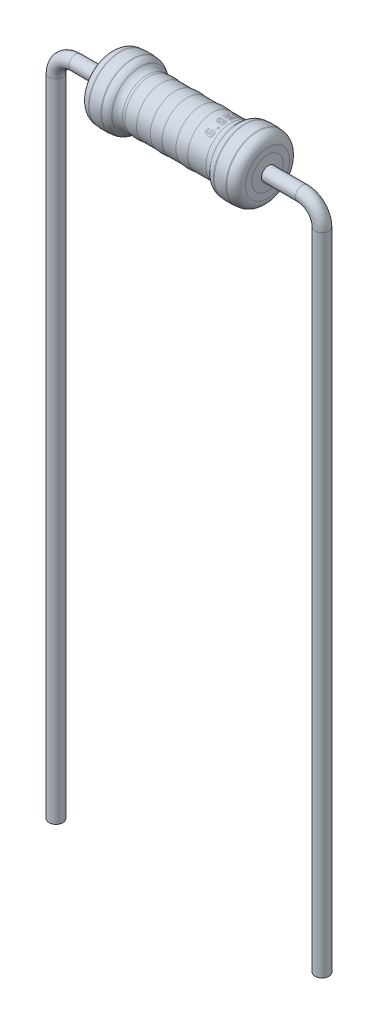
SolidWorks part; units mm, degrees
material "Plain Carbon Steel"
ref_plane "Front Plane" through (0, 0, 0) normal (0, 0, 1) x (1, 0, 0)
ref_plane "Top Plane" through (0, 0, 0) normal (0, 1, 0) x (1, 0, 0)
ref_plane "Right Plane" through (0, 0, 0) normal (1, 0, 0) x (0, 0, -1)
sketch "Sketch1" plane through (0, 0, 0) normal (0, 0, 1) x (1, 0, 0)
  line L0 (-4.33, 0) -> (4.33, 0)
  line L1 (-5.08, -0.75) -> (-5.08, -25.4)
  line L2 (5.08, -0.75) -> (5.08, -25.4)
  line L3 (-5.08, -25.4) -> (5.08, -25.4) construction
  line L4 (0, 0) -> (0, -25.4) construction
  arc A0 (-4.33, 0) -> (-5.08, -0.75) centre (-4.33, -0.75) ccw
  arc A1 (4.33, 0) -> (5.08, -0.75) centre (4.33, -0.75) cw
  dimension "D2" = 0.75
  dimension "D1" = 10.16
  dimension "D3" = 25.4
ref_plane "Plane1" through (-5.08, -25.4, 0) normal (0, -1, 0) x (-1, 0, 0)
sketch "Sketch2" plane through (-5.08, -25.4, 0) normal (0, -1, 0) x (-1, 0, 0)
  circle A0 centre (0, 0) radius 0.265
  dimension "D1" = 0.53
sweep "Sweep1" add profiles "Sketch2" path "Sketch1"
sketch "Sketch3" plane through (0, 0, 0) normal (0, 0, 1) x (1, 0, 0)
  line L0 (-3, 0) -> (3, 0)
  line L5 (-3, 0) -> (-3, 1.2)
  line L6 (3, 0) -> (3, 1.2)
  line L7 (-3, 1.2) -> (-1.8, 1.2)
  line L8 (3, 1.2) -> (1.8, 1.2)
  line L9 (-1.8, 1.2) -> (-1.8, 0.95)
  line L10 (-1.8, 0.95) -> (1.8, 0.95)
  line L11 (1.8, 0.95) -> (1.8, 1.2)
  line L12 (0, 0) -> (0, 0.95) construction
  dimension "D1" = 6
  dimension "D2" = 1.2
  dimension "D3" = 3.6
  dimension "D4" = 0.95
  dimension "D5" = 0.25
revolve "Revolve1" add sketch "Sketch3" angle 360 about L0
fillet "Fillet-1" radius 0.35 2 edges at (1.8, 0, 1.2) (-1.8, 0, 1.2)
fillet "Fillet-2" radius 0.36 4 edges at (3, 0, 1.2) (-3, 0, 1.2) (1.8, 0, 0.95) (-1.8, 0, 0.95)
sketch "Sketch5" plane through (0, 0, 0) normal (0, 0, 1) x (1, 0, 0)
  line L0 (-2.64, -1.2) -> (-2.1354, -1.2) construction
  line L5 (-2.3877, -1.2) -> (-2.3877, 0) construction
  line L10 (-3, 1.2) -> (-1.8, 1.2) construction
  line L15 (-1.05, 0.95) -> (-0.525, 0.95) construction
  line L16 (-3, 0) -> (3, 0) construction
  line L17 (-2.6127, 1.2) -> (-2.1627, 1.2) construction
  line L18 (-2.6127, 1.2) -> (-2.6127, 0) construction
  line L19 (-2.6127, 0) -> (-2.1627, 0) construction
  line L20 (-2.1627, 1.2) -> (-2.1627, 0) construction
  line L21 (-1.8, 0.95) -> (1.8, 0.95) construction
  line L22 (2.6127, 1.2) -> (2.1627, 1.2) construction
  line L23 (2.6127, 1.2) -> (2.6127, 0) construction
  line L24 (2.6127, 0) -> (2.1627, 0) construction
  line L25 (2.1627, 1.2) -> (2.1627, 0) construction
  line L26 (-1.05, 0.95) -> (-1.5, 0.95) construction
  line L27 (-1.05, 0.95) -> (-1.05, 0) construction
  line L28 (-1.05, 0) -> (-1.5, 0) construction
  line L29 (-1.5, 0.95) -> (-1.5, 0) construction
  line L30 (-2.3877, 1.2) -> (-2.3877, 1.22) construction
  line L31 (-0.075, 0.95) -> (-0.525, 0.95) construction
  line L32 (-0.075, 0.95) -> (-0.075, 0) construction
  line L33 (-0.075, 0) -> (-0.525, 0) construction
  line L34 (-0.525, 0.95) -> (-0.525, 0) construction
  line L35 (-1.275, 0.95) -> (-1.275, 0.97) construction
  line L36 (-0.3, 0.95) -> (-0.3, 0.97) construction
  line L37 (2.3877, 1.2) -> (2.3877, 1.22) construction
  line L39 (2.1354, -1.2) -> (2.64, -1.2) construction
  line L41 (2.3877, -1.2) -> (2.3877, 0) construction
  line L44 (3, 1.2) -> (1.8, 1.2) construction
  line L46 (-0.075, 0.95) -> (0.45, 0.95) construction
  line L48 (-3, 0) -> (-3, 0.6)
  line L49 (-3, 0) -> (-3, 1.2) construction
  line L50 (-3, 0) -> (-3.05, 0)
  line L51 (-3.05, 0) -> (-3.05, 0.2)
  line L52 (3, 0) -> (3.05, 0)
  line L53 (3.05, 0) -> (3.05, 0.2)
  line L54 (3, 0) -> (3, 0.6)
  line L55 (3, 0) -> (3, 1.2) construction
  line L56 (-1.05, 0) -> (-0.525, 0) construction
  line L58 (-0.075, 0) -> (0.45, 0) construction
  line L59 (0.45, 0) -> (0.45, 0.95) construction
  line L60 (0.45, 0) -> (0.9, 0) construction
  line L61 (0.9, 0) -> (0.9, 0.95) construction
  line L62 (1.5946, 0.95) -> (-1.5946, 0.95) construction
  line L63 (0.9, 0.95) -> (0.45, 0.95) construction
  line L64 (0.675, 0.95) -> (0.675, 0.97) construction
  arc A0 (-2.6127, 1.2) -> (-2.1627, 1.2) centre (-2.3877, -0.0556) cw construction
  arc A1 (-1.5, 0.95) -> (-1.05, 0.95) centre (-1.275, -0.3056) cw construction
  arc A2 (-0.525, 0.95) -> (-0.075, 0.95) centre (-0.3, -0.3056) cw construction
  arc A3 (2.1627, 1.2) -> (2.6127, 1.2) centre (2.3877, -0.0556) cw construction
  arc A6 (-3, 0.6) -> (-3.05, 0.2) centre (-4.625, 0.6) cw
  arc A7 (3.05, 0.2) -> (3, 0.6) centre (4.625, 0.6) cw
  arc A8 (0.45, 0.95) -> (0.9, 0.95) centre (0.675, -0.3056) cw construction
  dimension "D4" = 0.02
  dimension "D5" = 0.05
  dimension "D7" = 0.6
  dimension "D2" = 1.5
  dimension "D3" = 2.4
  dimension "D1" = 0.45
  dimension "D6" = 0.2
revolve "Revolve Ends" add sketch "Sketch5" angle 360 about L19
sketch "Sketch12" plane through (0, 0, 0) normal (0, 0, 1) x (1, 0, 0)
  line L0 (-2.6127, 0) -> (-2.1627, 0) construction
  line L1 (-2.6127, 0) -> (-2.1627, 0)
  line L2 (-2.6127, 1.2) -> (-2.6127, 0) construction
  line L3 (-2.6127, 1.2) -> (-2.6127, 0)
  line L4 (-2.1627, 1.2) -> (-2.1627, 0) construction
  line L5 (-2.1627, 1.2) -> (-2.1627, 0)
  arc A0 (-2.1627, 1.2) -> (-2.6127, 1.2) centre (-2.3877, -0.0556) ccw construction
  arc A1 (-2.1627, 1.2) -> (-2.6127, 1.2) centre (-2.3877, -0.0556) ccw
revolve "Revolve BAND 1" add sketch "Sketch12" angle 360 about L19
sketch "Sketch7" plane through (0, 0, 0) normal (0, 0, 1) x (1, 0, 0)
  line L0 (-1.05, 0) -> (-1.5, 0) construction
  line L1 (-1.05, 0.95) -> (-1.05, 0) construction
  line L2 (-1.5, 0.95) -> (-1.5, 0) construction
  line L3 (-1.05, 0.95) -> (-1.05, 0)
  line L4 (-1.5, 0.95) -> (-1.5, 0)
  line L5 (-1.05, 0) -> (-1.5, 0)
  arc A0 (-1.05, 0.95) -> (-1.5, 0.95) centre (-1.275, -0.3056) ccw construction
  arc A1 (-1.05, 0.95) -> (-1.5, 0.95) centre (-1.275, -0.3056) ccw
revolve "Revolve BAND 2" add sketch "Sketch7" angle 360 about L28
sketch "Sketch8" plane through (0, 0, 0) normal (0, 0, 1) x (1, 0, 0)
  line L0 (-0.075, 0.95) -> (-0.075, 0) construction
  line L1 (-0.075, 0) -> (-0.525, 0) construction
  line L2 (-0.525, 0.95) -> (-0.525, 0) construction
  line L3 (-0.075, 0.95) -> (-0.075, 0)
  line L4 (-0.075, 0) -> (-0.525, 0)
  line L5 (-0.525, 0.95) -> (-0.525, 0)
  arc A0 (-0.075, 0.95) -> (-0.525, 0.95) centre (-0.3, -0.3056) ccw construction
  arc A1 (-0.075, 0.95) -> (-0.525, 0.95) centre (-0.3, -0.3056) ccw
revolve "Revolve BAND 3" add sketch "Sketch8" angle 360 about L33
sketch "Sketch9" plane through (0, 0, 0) normal (0, 0, 1) x (1, 0, 0)
  line L0 (0.9, 0) -> (0.9, 0.95) construction
  line L1 (0.45, 0) -> (0.45, 0.95) construction
  line L2 (0.45, 0) -> (0.9, 0) construction
  line L3 (0.9, 0) -> (0.9, 0.95)
  line L4 (0.45, 0) -> (0.45, 0.95)
  line L5 (0.45, 0) -> (0.9, 0)
  arc A0 (0.9, 0.95) -> (0.45, 0.95) centre (0.675, -0.3056) ccw construction
  arc A1 (0.9, 0.95) -> (0.45, 0.95) centre (0.675, -0.3056) ccw
revolve "Revolve BAND 4" add sketch "Sketch9" angle 360 about L60
sketch "Sketch11" plane through (0, 0, 0) normal (0, 0, 1) x (1, 0, 0)
  line L0 (2.6127, 1.2) -> (2.6127, 0) construction
  line L1 (2.1627, 1.2) -> (2.1627, 0) construction
  line L2 (2.6127, 0) -> (2.1627, 0) construction
  line L3 (2.6127, 1.2) -> (2.6127, 0)
  line L4 (2.1627, 1.2) -> (2.1627, 0)
  line L5 (2.6127, 0) -> (2.1627, 0)
  arc A0 (2.6127, 1.2) -> (2.1627, 1.2) centre (2.3877, -0.0556) ccw construction
  arc A1 (2.6127, 1.2) -> (2.1627, 1.2) centre (2.3877, -0.0556) ccw
revolve "Revolve5" add sketch "Sketch11" angle 360 about L24
ref_plane "Plane2" through (0, 2, 0) normal (0, 1, 0) x (1, 0, 0)
sketch "Sketch6" plane through (0, 2, 0) normal (0, 1, 0) x (1, 0, 0)
  line L0 (0, 0) -> (1.5, 0) construction
  line L1 (1.5, 1) -> (1.5, -1) construction
  text T0 "6.8KΩ" font "Calibri" height 0.3
  dimension "D1" = 1.5
  dimension "D2" = 2
wrap "Wrap1" sketch "Sketch6" wrap type scribe source sketch "Sketch6" face at (1.5946, 0, 0.95)
